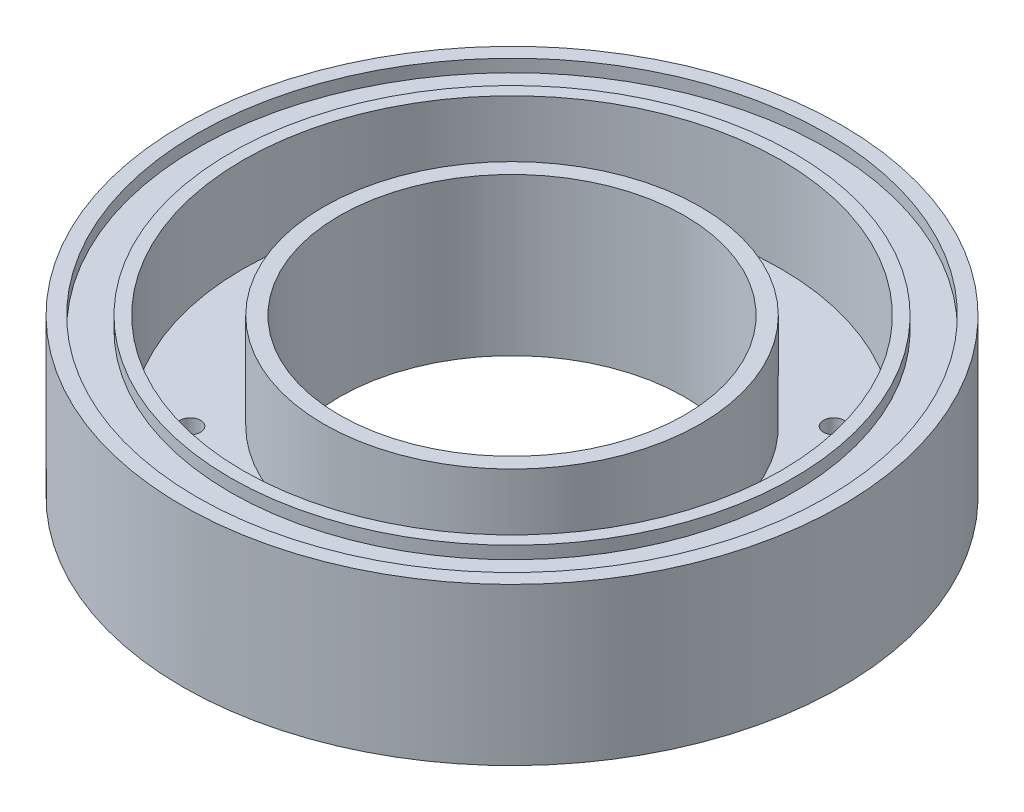
SolidWorks part; units mm, degrees
ref_plane "Front" through (0, 0, 0) normal (0, 0, 1) x (1, 0, 0)
ref_plane "Top" through (0, 0, 0) normal (0, 1, 0) x (1, 0, 0)
ref_plane "Right" through (0, 0, 0) normal (1, 0, 0) x (0, 0, -1)
sketch "Sketch1" plane through (0, 0, 0) normal (0, 1, 0) x (1, 0, 0)
  circle A1 centre (0, 0) radius 52.5
  dimension "D2" = 105
extrude "Boss-Extrude1" add sketch "Sketch1" along normal blind 30
sketch "Sketch2" plane through (0, 30, 0) normal (0, 1, 0) x (1, 0, 0)
  line L0 (-59.3565, 0) -> (66.87, 0) construction
  circle A0 centre (0, 0) radius 50.175
  circle A1 centre (0, 0) radius 44.85
  point P6 (-44.85, 0)
  point P7 (-50.175, 0)
  dimension "D1" = 100.35
  dimension "D2" = 89.7
  dimension "D3" = 5.325
extrude "Cut-Extrude1" cut sketch "Sketch2" against normal blind 7
sketch "Sketch3" plane through (0, 30, 0) normal (0, 1, 0) x (1, 0, 0)
  circle A0 centre (0, 0) radius 42.85
  circle A1 centre (0, 0) radius 30
  dimension "D1" = 85.7
  dimension "D2" = 60
extrude "Cut-Extrude2" cut sketch "Sketch3" against normal blind 20
sketch "Sketch6" plane through (0, 30, 0) normal (0, 1, 0) x (1, 0, 0)
  line L0 (-66.0113, 0) -> (76.7448, 0) construction
  circle A0 centre (0, 0) radius 27.5
  circle A1 centre (0, 0) radius 30 construction
  point P5 (-27.5, 0)
  point P6 (-30, 0)
  dimension "D1" = 2.5
extrude "Cut-Extrude6" cut sketch "Sketch6" against normal through all
ref_axis "Axis1" through (0, 10, 0) along (0, 1, 0)
sketch "Sketch9" plane through (0, 0, 0) normal (0, -1, 0) x (1, 0, 0)
  line L1 (-25.635, -25.635) -> (25.635, -25.635) construction
  line L2 (-25.635, -25.635) -> (-25.635, 25.635) construction
  line L3 (-25.635, 25.635) -> (25.635, 25.635) construction
  line L4 (25.635, -25.635) -> (25.635, 25.635) construction
  line L5 (-25.635, -25.635) -> (25.635, 25.635) construction
  line L6 (-25.635, 25.635) -> (25.635, -25.635) construction
  circle A0 centre (-25.635, 25.635) radius 1.65
  circle A1 centre (25.635, 25.635) radius 1.65
  circle A2 centre (25.635, -25.635) radius 1.65
  circle A3 centre (-25.635, -25.635) radius 1.65
  point P0 (0, 0)
  dimension "D3" = 3.3
  dimension "D4" = 3.3
  dimension "D5" = 3.3
  dimension "D6" = 3.3
  dimension "D1" = 51.27
  dimension "D2" = 51.27
extrude "Cut-Extrude7" cut sketch "Sketch9" against normal blind 10
sketch "Sketch10" plane through (0, 0, 0) normal (0, -1, 0) x (1, 0, 0)
  circle A0 centre (-25.635, 25.635) radius 3
  circle A1 centre (25.635, 25.635) radius 3
  circle A2 centre (25.635, -25.635) radius 3
  circle A3 centre (-25.635, -25.635) radius 3
  dimension "D1" = 6
  dimension "D2" = 6
  dimension "D3" = 6
  dimension "D4" = 6
extrude "Cut-Extrude8" cut sketch "Sketch10" against normal blind 4
sketch "Sketch12" plane through (0, 30, 0) normal (0, 1, 0) x (1, 0, 0)
  line L1 (-65.2799, -62.7964) -> (65.2799, -62.7964)
  line L2 (-65.2799, -62.7964) -> (-65.2799, 62.7964)
  line L3 (-65.2799, 62.7964) -> (65.2799, 62.7964)
  line L4 (65.2799, -62.7964) -> (65.2799, 62.7964)
  line L5 (-65.2799, -62.7964) -> (65.2799, 62.7964) construction
  line L6 (-65.2799, 62.7964) -> (65.2799, -62.7964) construction
  point P0 (0, 0)
extrude "Cut-Extrude9" cut sketch "Sketch12" against normal blind 5
sketch "Sketch13" plane through (0, 10, 0) normal (0, 1, 0) x (1, 0, 0)
  circle A0 centre (0, 0) radius 30
  circle A1 centre (-0.5913, 0) radius 43.4413
extrude "Cut-Extrude10" cut sketch "Sketch13" against normal blind 0.3
sketch "Sketch8" plane through (0, 30, 0) normal (0, 1, 0) x (1, 0, 0)
  line L8 (-4.85, -29.65) -> (-4.85, -39.35)
  line L9 (4.85, -29.65) -> (-4.85, -29.65)
  line L10 (4.85, -39.35) -> (4.85, -29.65)
  line L11 (-4.85, -39.35) -> (4.85, -39.35)
  line L12 (-4.85, -29.6054) -> (-4.85, -39.35)
  line L14 (4.85, -39.35) -> (4.85, -29.6054)
  line L15 (-4.85, -39.35) -> (4.85, -39.35)
  arc A0 (4.85, -29.6054) -> (-4.85, -29.6054) centre (0, 0) cw
  circle A1 centre (0, 0) radius 30 construction
  dimension "D1" = 0.15
extrude "Boss-Extrude2" [suppressed] add sketch "Sketch8" against normal up to surface (20 mm away)
